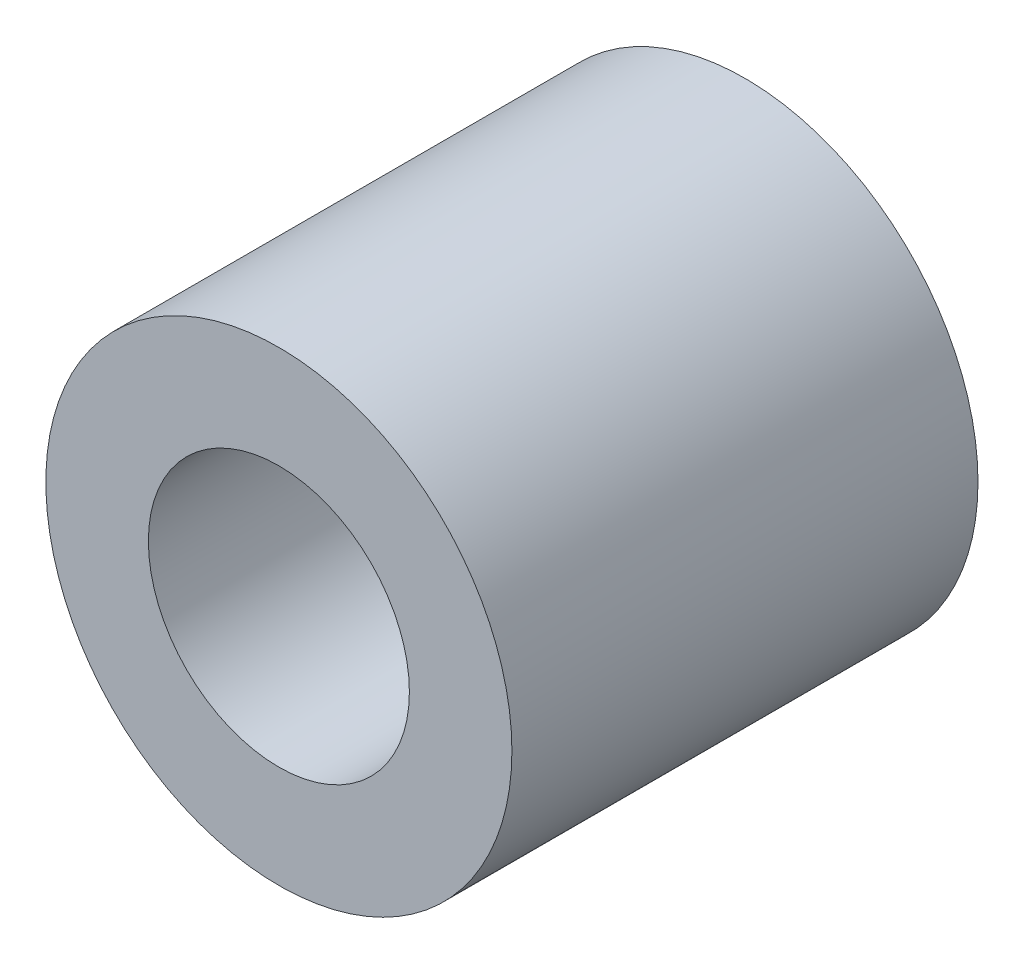
SolidWorks part; units mm, degrees
ref_plane "Front Plane" through (0, 0, 0) normal (0, 0, 1) x (1, 0, 0)
ref_plane "Top Plane" through (0, 0, 0) normal (0, 1, 0) x (1, 0, 0)
ref_plane "Right Plane" through (0, 0, 0) normal (1, 0, 0) x (0, 0, -1)
sketch "Sketch1" plane through (0, 0, 0) normal (0, 0, 1) x (1, 0, 0)
  circle A0 centre (0, 0) radius 3.175
  circle A1 centre (0, 0) radius 1.778
  dimension "OD" = 6.35
  dimension "ID" = 3.556
extrude "Extrude1" add sketch "Sketch1" along normal mid plane 6.35
sketch "Sketch2" plane through (0, 0, 0) normal (1, 0, 0) x (0, 0, -1)
  line L0 (-3.175, -1.778) -> (3.175, -1.778) construction
  line L3 (3.175, 1.778) -> (-3.175, 1.778) construction
  line L5 (-3.175, -1.778) -> (3.175, -1.778)
  line L6 (3.175, 1.778) -> (-3.175, 1.778)
sketch "Sketch4" plane through (0, 0, 3.175) normal (0, 0, 1) x (1, 0, 0)
  line L0 (0, 0) -> (-1.2572, 1.2572)
  line L1 (0, -0.8731) -> (0, 0.8731) construction
  circle A0 centre (0, 0) radius 1.778 construction
  dimension "D1" = 45
